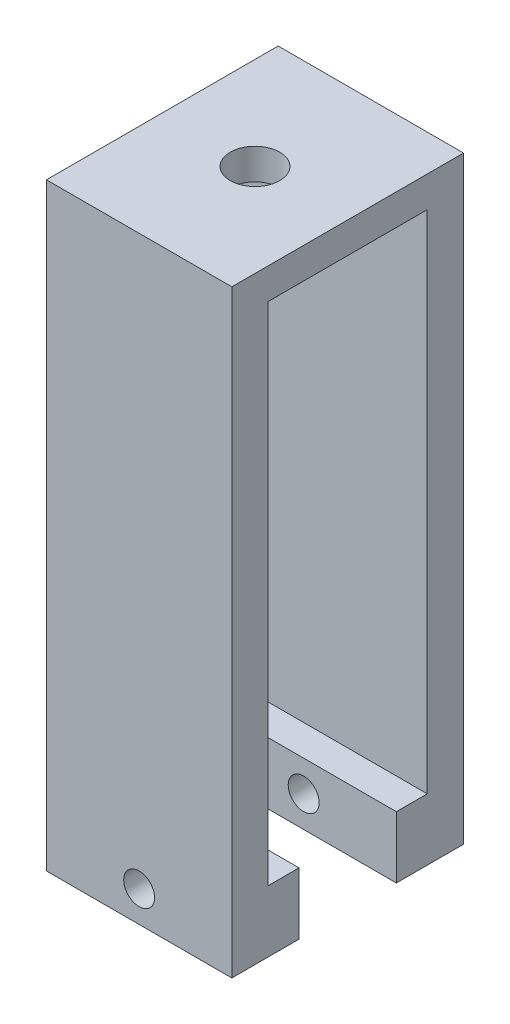
SolidWorks part; units mm, degrees
ref_plane "Plan de face" through (0, 0, 0) normal (0, 0, 1) x (1, 0, 0)
ref_plane "Plan de dessus" through (0, 0, 0) normal (0, 1, 0) x (1, 0, 0)
ref_plane "Plan de droite" through (0, 0, 0) normal (1, 0, 0) x (0, 0, -1)
sketch "Esquisse1" plane through (0, 0, 0) normal (0, 0, 1) x (1, 0, 0)
  line L0 (6, 0) -> (-6, 0)
  line L1 (6, 0) -> (6, 38.75)
  line L6 (0, 12) -> (0, 0) construction
  line L9 (-6, 0) -> (-6, 38.75)
  line L10 (6, 38.75) -> (-6, 38.75)
  dimension "D1" = 38.75
  dimension "D3" = 6
extrude "Boss.-Extru.1" add sketch "Esquisse1" along normal blind 15
sketch "Esquisse2" plane through (6, 0, 0) normal (1, 0, 0) x (0, 0, -1)
  line L3 (-12.65, 36.75) -> (-2.35, 36.75)
  line L5 (-15, 38.75) -> (0, 38.75) construction
  line L6 (-12.65, 36.75) -> (-12.65, 4)
  line L7 (-12.65, 4) -> (-10.65, 4)
  line L8 (-10.65, 4) -> (-10.65, 0)
  line L9 (-15, 0) -> (0, 0) construction
  line L10 (-10.65, 0) -> (-4.35, 0)
  line L11 (-4.35, 0) -> (-4.35, 4)
  line L12 (-4.35, 4) -> (-2.35, 4)
  line L13 (-2.35, 36.75) -> (-2.35, 4)
  dimension "D1" = 6.3
  dimension "D2" = 4.35
  dimension "D3" = 2
  dimension "D4" = 4
  dimension "D5" = 4
  dimension "D6" = 2
  dimension "D7" = 2
extrude "Enlèv. mat.-Extru.1" cut sketch "Esquisse2" against normal through all
sketch "Esquisse3" plane through (0, 0, 0) normal (0, 0, -1) x (-1, 0, 0)
  circle A0 centre (0, 2) radius 1
  dimension "D2" = 2
  dimension "D1" = 2
extrude "Enlèv. mat.-Extru.2" cut sketch "Esquisse3" against normal through all
sketch "Esquisse5" plane through (0, 36.75, 0) normal (0, -1, 0) x (1, 0, 0)
  line L7 (6, 4.35) -> (6, 0) construction
  circle A0 centre (0, 7.5) radius 1.6
  point P4 (-9.7592, 11.6415)
  dimension "D1" = 3.2
  dimension "D2" = 6
  dimension "D3" = 7.5
extrude "Enlèv. mat.-Extru.3" cut sketch "Esquisse5" against normal through all
